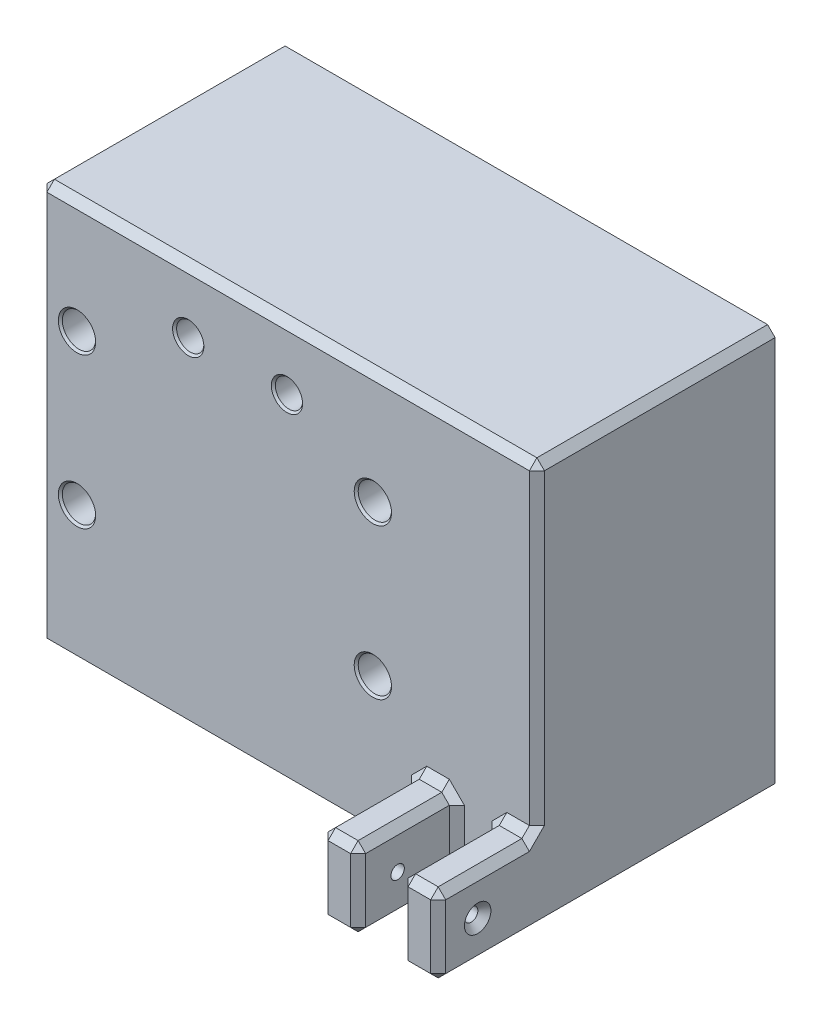
SolidWorks part; units mm, degrees
ref_plane "Front Plane" through (0, 0, 0) normal (0, 0, 1) x (1, 0, 0)
ref_plane "Top Plane" through (0, 0, 0) normal (0, 1, 0) x (1, 0, 0)
ref_plane "Right Plane" through (0, 0, 0) normal (1, 0, 0) x (0, 0, -1)
sketch "Sketch1" plane through (0, 0, 0) normal (0, 0, 1) x (1, 0, 0)
  line L0 (-62.9995, 50.8) -> (-50.2995, 50.8) construction
  line L1 (62.9995, 50.8) -> (-62.9995, 50.8)
  line L2 (62.9995, 50.8) -> (62.9995, -50.8)
  line L3 (62.9995, -50.8) -> (-62.9995, -50.8)
  line L4 (-62.9995, 50.8) -> (-62.9995, -50.8)
  line L5 (62.9995, 50.8) -> (-62.9995, -50.8) construction
  line L6 (62.9995, -50.8) -> (-62.9995, 50.8) construction
  line L7 (-50.2995, 66.675) -> (-24.8995, 66.675) construction
  line L8 (-50.2995, 66.675) -> (-50.2995, 41.275) construction
  line L9 (-50.2995, 41.275) -> (-24.8995, 41.275) construction
  line L10 (-24.8995, 66.675) -> (-24.8995, 41.275) construction
  line L11 (-50.2995, 50.8) -> (-50.2995, 41.275) construction
  line L12 (-50.2995, 41.275) -> (-12.7995, 41.275) construction
  line L13 (-12.7995, 41.275) -> (-12.7995, 28.575) construction
  line L14 (-12.7995, 28.575) -> (-62.9995, 28.575) construction
  line L15 (-62.9995, 28.575) -> (-62.9995, 50.8) construction
  line L16 (-12.7995, 41.275) -> (-12.7995, 28.575) construction
  line L17 (-12.7995, 28.575) -> (56.8505, 28.575) construction
  line L18 (56.8505, 28.575) -> (56.8505, 41.275) construction
  line L19 (56.8505, 41.275) -> (-12.7995, 41.275) construction
  line L20 (-25.2995, 34.925) -> (-12.7995, 34.925) construction
  line L21 (-12.7995, 34.925) -> (-0.2995, 34.925) construction
  line L22 (56.8505, 34.925) -> (50.5005, 34.925) construction
  line L23 (42.7245, -40.8) -> (53.4745, -40.8) construction
  line L24 (62.9995, -50.8) -> (53.4745, -50.8)
  line L25 (62.9995, -50.8) -> (62.9995, -30.8)
  line L26 (62.9995, -30.8) -> (53.4745, -30.8)
  line L27 (53.4745, -50.8) -> (53.4745, -30.8)
  line L29 (53.4745, -30.8) -> (53.4745, -50.8) construction
  line L30 (53.4745, -50.8) -> (42.7245, -50.8) construction
  line L31 (42.7245, -30.8) -> (42.7245, -50.8) construction
  line L32 (42.7245, -50.8) -> (33.1995, -50.8)
  line L33 (42.7245, -50.8) -> (42.7245, -30.8)
  line L34 (42.7245, -30.8) -> (33.1995, -30.8)
  line L35 (33.1995, -50.8) -> (33.1995, -30.8)
  line L36 (48.0995, -40.8) -> (48.0995, -30.8) construction
  line L37 (48.0995, -40.8) -> (46.3372, 14.7841) construction
  line L38 (48.0995, -40.8) -> (50.5005, 34.925) construction
  line L39 (42.7245, -30.8) -> (53.4745, -30.8) construction
  line L40 (-25.2995, 34.925) -> (-54.2252, 41.275) construction
  line L41 (-25.2995, 34.925) -> (-50.2995, 50.8) construction
  line L43 (-53.4745, 22.225) -> (21.4555, 22.225) construction
  line L44 (-53.4745, 22.225) -> (-53.4745, -15.875) construction
  line L45 (-53.4745, -15.875) -> (21.4555, -15.875) construction
  line L46 (21.4555, 22.225) -> (21.4555, -15.875) construction
  circle A0 centre (-25.2995, 34.925) radius 3.45
  circle A1 centre (-0.2995, 34.925) radius 3.45
  circle A2 centre (50.5005, 34.925) radius 1.5
  arc A3 (-50.2995, 50.8) -> (-54.2252, 41.275) centre (-25.2995, 34.925) ccw construction
  arc A4 (50.5005, 34.925) -> (46.3372, 14.7841) centre (-0.2995, 34.925) cw construction
  arc A5 (48.0995, -30.8) -> (47.7826, -30.805) centre (48.0995, -40.8) ccw construction
  arc A6 (48.0995, -30.8) -> (48.4164, -30.805) centre (48.0995, -40.8) cw construction
  circle A7 centre (21.4555, 22.225) radius 1.27
  circle A8 centre (21.4555, -15.875) radius 1.27
  circle A9 centre (-53.4745, -15.875) radius 1.27
  circle A10 centre (-53.4745, 22.225) radius 1.27
  point P0 (0, 0)
  dimension "D12" = 6.9
  dimension "D13" = 3
  dimension "D19" = 2.54
  dimension "D1" = 25.4
  dimension "D2" = 25
  dimension "D3" = 12.5
  dimension "D4" = 50.8
  dimension "D5" = 6.35
  dimension "D6" = 9.525
  dimension "D7" = 12.7
  dimension "D8" = 12.7
  dimension "D9" = 10.75
  dimension "D10" = 20
  dimension "D11" = 101.6
  dimension "D16" = 9.525
  dimension "D17" = 125.9991
  dimension "D18" = 20.034
  dimension "D20" = 38.1
  dimension "D21" = 74.93
  dimension "D22" = 9.525
  dimension "D23" = 12.7
  dimension "D14" = 10.3549
  dimension "D15" = 20.7098
extrude "Boss-Extrude1" add sketch "Sketch1" against normal blind 60.325 contours A0 | A1 | L3 L4 L1 L2 | A10 | A9 | A8 | A7 region at (-25.2995, 34.925, 0) region at (-0.2995, 34.925, 0)
extrude "Boss-Extrude2" add sketch "Sketch1<3>" along normal blind 25 contours L35 L3 L33 L34 | L27 L3 L2 L26 region at (58.237, -40.8, 0) region at (37.962, -40.8, 0)
sketch "Sketch1<3>" plane through (0, 0, 0) normal (0, 0, 1) x (1, 0, 0) same geometry as "Sketch1"
sketch "Sketch2" plane through (62.9995, 0, 0) normal (1, 0, 0) x (0, 0, -1)
  line L0 (-25, -40.8) -> (-15, -40.8) construction
  line L1 (-25, -30.8) -> (-25, -50.8) construction
  circle A0 centre (-15, -40.8) radius 1.6
  circle A1 centre (-15, -40.8) radius 10 construction
  dimension "D1" = 20
  dimension "D2" = 3.2
extrude "Cut-Extrude1" cut sketch "Sketch2" against normal through all both and the other way through all
hole_wizard "CSK for #8 Flat Head Machine Screw (100)1" positions "Sketch4" profile "Sketch6" countersink size "#8" standard "ANSI Inch" end condition through all
sketch "Sketch4" plane through (0, 0, 0) normal (0, 0, 1) x (1, 0, 0)
  point P0 (-53.4745, 22.225)
  point P3 (-53.4745, -15.875)
  point P6 (21.4555, -15.875)
  point P9 (21.4555, 22.225)
sketch "Sketch6" plane through (-53.4745, 22.225, 0) normal (1, 0, 0) x (0, -1, 0)
  line L0 (0, 0) -> (0, 60.325)
  line L1 (0, 60.325) -> (2.2479, 60.325)
  line L2 (2.2479, 60.325) -> (2.2479, 39.7518)
  line L3 (2.2479, 39.7518) -> (4.2164, 38.1)
  line L4 (4.2164, 38.1) -> (4.2164, 0)
  line L6 (4.2164, 0) -> (0, 0)
  line L7 (-2.2479, 39.7518) -> (-4.2164, 38.1) construction
  line L11 (0, -6.35) -> (0, 107.95) construction
  dimension "Thru Hole Dia." = 4.4958
  dimension "Thru Hole Depth" = 60.325
  dimension "C'Sink Dia." = 8.4328
  dimension "C'Sink Angle" = 100
  dimension "Head Clearance" = 38.1
hole_wizard "CSK for M3 Flat Head Machine Screw1" positions "Sketch7" profile "Sketch8" countersink size "M3" standard "ANSI Metric" end condition through all
sketch "Sketch7" plane through (62.9995, 0, 0) normal (1, 0, 0) x (0, 0, -1)
  point P0 (-15, -40.8)
sketch "Sketch8" plane through (62.9995, -40.8, 15) normal (0, 1, 0) x (0, 0, -1)
  line L0 (0, 0) -> (0, 125.9991)
  line L1 (0, 125.9991) -> (1.7, 125.9991)
  line L2 (1.7, 125.9991) -> (1.7, 1.65)
  line L3 (1.7, 1.65) -> (3.35, 0)
  line L5 (3.35, 0) -> (0, 0)
  line L6 (-1.7, 1.65) -> (-3.35, 0) construction
  line L11 (0, -6.35) -> (0, 107.95) construction
  dimension "Thru Hole Dia." = 3.4
  dimension "Thru Hole Depth" = 125.9991
  dimension "Near C'Sink Dia." = 6.7
  dimension "Near C'Sink Angle" = 90
chamfer "Chamfer1" distance 0.508 angle 45 6 edges at (3.1505, 34.925, 0) (-21.8495, 34.925, 0) (25.6719, -15.875, 0) (-49.2581, 22.225, 0) (-49.2581, -15.875, 0) (25.6719, 22.225, 0)
chamfer "Chamfer2" distance 1.905 angle 45 29 edges at (53.4745, -50.8, 12.5) (42.7245, -50.8, 12.5) (48.0995, -50.8, 0) (53.4745, -40.8, 0) (42.7245, -40.8, 0) (33.1995, -50.8, 12.5) (62.9995, -30.8, 12.5) (58.237, -30.8, 25) (62.9995, -40.8, 25) (62.9995, -50.8, -17.6625) (58.237, -50.8, 25) (53.4745, -40.8, 25) (53.4745, -30.8, 12.5) (58.237, -30.8, 0) (42.7245, -30.8, 12.5) (37.962, -30.8, 25) (42.7245, -40.8, 25) (37.962, -50.8, 25) (33.1995, -40.8, 25) (33.1995, -30.8, 12.5) (37.962, -30.8, 0) (-62.9995, 50.8, -30.1625) (-62.9995, -50.8, -30.1625) (62.9995, 50.8, -30.1625) (33.1995, -40.8, 0) (62.9995, 10, 0) (-14.9, -50.8, 0) (-62.9995, 0, 0) (0, 50.8, 0)
equation "\"D15@Sketch1\"=\"D14@Sketch1\"*2"
equation "\"D3@Sketch1\"=\"D2@Sketch1\"/2"
